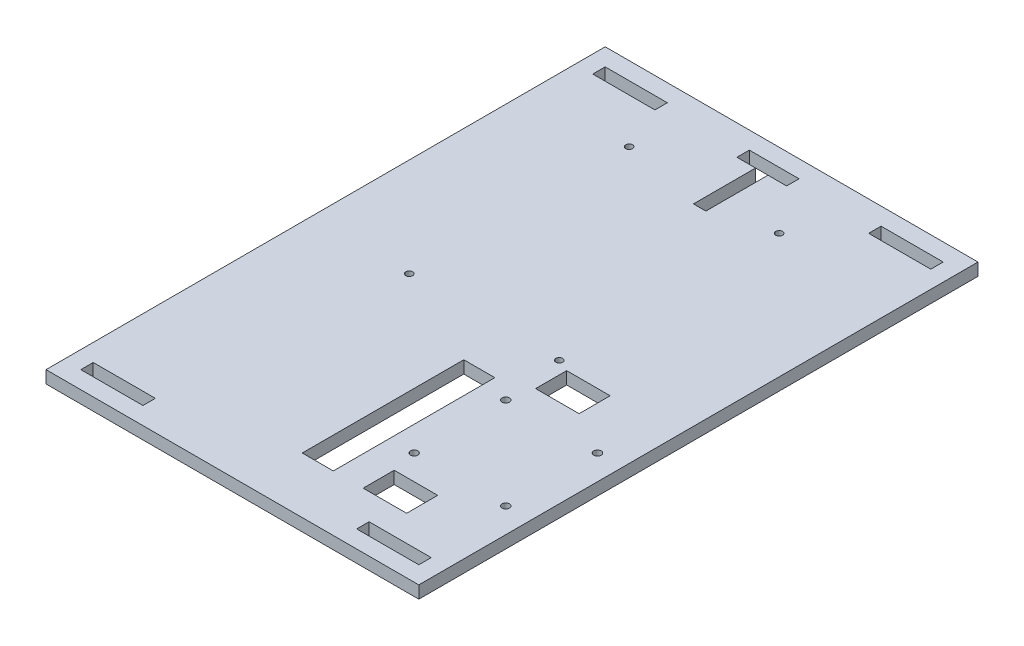
SolidWorks part; units mm, degrees
ref_plane "Front Plane" through (0, 0, 0) normal (0, 0, 1) x (1, 0, 0)
ref_plane "Top Plane" through (0, 0, 0) normal (0, 1, 0) x (1, 0, 0)
ref_plane "Right Plane" through (0, 0, 0) normal (1, 0, 0) x (0, 0, -1)
sketch "Sketch1" plane through (0, 0, 0) normal (0, 1, 0) x (1, 0, 0)
  line L1 (-75, 112.5) -> (75, 112.5)
  line L2 (-75, 112.5) -> (-75, -112.5)
  line L3 (-75, -112.5) -> (75, -112.5)
  line L4 (75, 112.5) -> (75, -112.5)
  point P4 (0, 112.5)
  point P6 (-75, 0)
  dimension "D1" = 150
  dimension "D2" = 225
extrude "Boss-Extrude1" add sketch "Sketch1" along normal blind 5
sketch "Sketch2" plane through (0, 5, 0) normal (0, 1, 0) x (1, 0, 0)
  line L0 (-35.35, 82.5) -> (25, 82.5) construction
  line L1 (-35.35, 82.5) -> (-35.35, -6) construction
  circle A0 centre (-35.35, 82.5) radius 1.375
  circle A1 centre (25, 82.5) radius 1.375
  circle A2 centre (25, -6) radius 1.375
  circle A3 centre (-35.35, -6) radius 1.375
  dimension "D3" = 2.75
  dimension "D1" = 60.35
  dimension "D2" = 88.5
  dimension "D4" = 30
  dimension "D5" = 50
sketch "Sketch3" plane through (0, 5, 0) normal (0, 1, 0) x (1, 0, 0)
  line L0 (28.1, -30.6) -> (28.1, -67.5) construction
  line L1 (28.1, -30.6) -> (65, -30.6) construction
  circle A0 centre (28.1, -30.6) radius 1.5
  circle A1 centre (65, -30.6) radius 1.5
  circle A2 centre (65, -67.5) radius 1.5
  circle A3 centre (28.1, -67.5) radius 1.5
  dimension "D1" = 3
  dimension "D2" = 36.9
  dimension "D3" = 45
  dimension "D4" = 10
sketch "Sketch6" plane through (0, 5, 0) normal (0, 1, 0) x (1, 0, 0)
  line L10 (-10, 105.5) -> (10, 105.5)
  line L11 (-10, 105.5) -> (-10, 100.5)
  line L12 (-10, 100.5) -> (10, 100.5)
  line L13 (10, 105.5) -> (10, 100.5)
  point P4 (0, 105.5)
  dimension "D1" = 20
  dimension "D2" = 7
  dimension "D3" = 5
extrude "Cut-Extrude1" cut sketch "Sketch2" against normal through all
extrude "Cut-Extrude2" cut sketch "Sketch3" against normal through all
extrude "Cut-Extrude3" cut sketch "Sketch6" against normal through all
sketch "Sketch9" plane through (0, 5, 0) normal (0, 1, 0) x (1, 0, 0)
  line L1 (5.6, -90) -> (18.1, -90)
  line L2 (5.6, -90) -> (5.6, -25)
  line L3 (5.6, -25) -> (18.1, -25)
  line L4 (18.1, -90) -> (18.1, -25)
  line L5 (30.1, -8.1) -> (47.6, -8.1)
  line L6 (30.1, -8.1) -> (30.1, -20.6)
  line L7 (30.1, -20.6) -> (47.6, -20.6)
  line L8 (47.6, -8.1) -> (47.6, -20.6)
  line L9 (30.1, -77.5) -> (47.6, -77.5)
  line L10 (30.1, -77.5) -> (30.1, -90)
  line L11 (30.1, -90) -> (47.6, -90)
  line L12 (47.6, -77.5) -> (47.6, -90)
  circle A0 centre (28.1, -30.6) radius 1.5 construction
  circle A1 centre (28.1, -67.5) radius 1.5 construction
  dimension "D1" = 2
  dimension "D5" = 10
  dimension "D2" = 12.5
  dimension "D3" = 17.5
  dimension "D4" = 10
  dimension "D6" = 10
  dimension "D7" = 12.5
  dimension "D8" = 65
extrude "Cut-Extrude4" cut sketch "Sketch9" against normal up to surface (5 mm away) up to face at (0, 0, -103)
sketch "Sketch10" plane through (0, 5, 0) normal (0, 1, 0) x (1, 0, 0)
  line L0 (0, 0) -> (-75, 0) construction
  line L1 (-68, -105.5) -> (-43, -105.5)
  line L2 (-68, -105.5) -> (-68, -100.5)
  line L3 (-68, -100.5) -> (-43, -100.5)
  line L4 (-43, -105.5) -> (-43, -100.5)
  line L9 (-75, 112.5) -> (-75, -112.5) construction
  line L10 (0, 0) -> (0, -112.5) construction
  line L11 (-75, -112.5) -> (75, -112.5) construction
  line L12 (-68, 100.5) -> (-43, 100.5)
  line L13 (-43, 105.5) -> (-43, 100.5)
  line L14 (-68, 105.5) -> (-43, 105.5)
  line L15 (-68, 105.5) -> (-68, 100.5)
  line L16 (68, -100.5) -> (43, -100.5)
  line L17 (43, -105.5) -> (43, -100.5)
  line L18 (68, -105.5) -> (43, -105.5)
  line L19 (68, -105.5) -> (68, -100.5)
  line L20 (68, 105.5) -> (68, 100.5)
  line L21 (68, 105.5) -> (43, 105.5)
  line L22 (43, 105.5) -> (43, 100.5)
  line L23 (68, 100.5) -> (43, 100.5)
  dimension "D1" = 7
  dimension "D2" = 7
  dimension "D3" = 5
  dimension "D4" = 25
extrude "Cut-Extrude5" cut sketch "Sketch10" against normal up to surface (5 mm away) up to face at (11.85, 0, 57.5)
sketch "Sketch11" plane through (0, 5, 0) normal (0, 1, 0) x (1, 0, 0)
  line L0 (-10, 100.5) -> (10, 100.5) construction
  line L1 (-2.5, 100.5) -> (2.5, 100.5)
  line L2 (2.5, 100.5) -> (2.5, 75.5)
  line L3 (2.5, 75.5) -> (-2.5, 75.5)
  line L4 (-2.5, 75.5) -> (-2.5, 100.5)
  point P6 (0, 100.5)
  point P9 (0, 100.5)
  dimension "D1" = 5
  dimension "D2" = 25
extrude "Cut-Extrude6" cut sketch "Sketch11" against normal up to surface (5 mm away) up to face at (-55.5, 0, -103)
